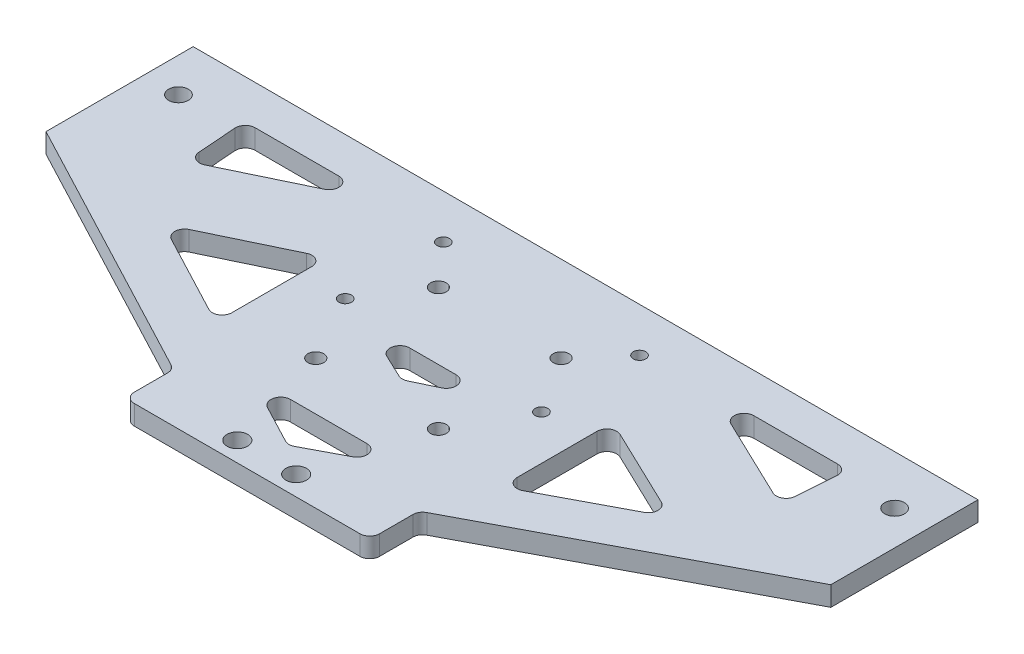
SolidWorks part; units mm, degrees
material "Thornel Mat VMA"
ref_plane "Front" through (0, 0, 0) normal (0, 0, 1) x (1, 0, 0)
ref_plane "Top" through (0, 0, 0) normal (0, 1, 0) x (1, 0, 0)
ref_plane "Right" through (0, 0, 0) normal (1, 0, 0) x (0, 0, -1)
sketch "草图1" plane through (0, 0, 0) normal (0, 1, 0) x (1, 0, 0)
  line L0 (0, 40.0348) -> (0, 0) construction
  line L1 (25, 0) -> (-25, 0)
  line L2 (-25, 0) -> (-80, 29)
  line L3 (-80, 29) -> (-80, 59)
  line L4 (-80, 59) -> (80, 59)
  line L5 (80, 29) -> (80, 59)
  line L6 (25, 0) -> (80, 29)
  point P9 (0, 59)
  dimension "D1" = 59
  dimension "D2" = 80
  dimension "D3" = 25
  dimension "D4" = 30
extrude "凸台-拉伸1" add sketch "草图1" along normal blind 4
sketch "草图2" plane through (0, 4, 0) normal (0, 1, 0) x (1, 0, 0)
  line L0 (0, 0) -> (0, 59) construction
  line L1 (80, 59) -> (-80, 59) construction
  line L2 (-12.5, 41.5) -> (-12.5, 16.5) construction
  line L3 (-12.5, 29) -> (12.5, 29) construction
  line L4 (12.5, 41.5) -> (12.5, 16.5) construction
  circle A0 centre (-12.5, 41.5) radius 1.6
  circle A3 centre (12.5, 41.5) radius 1.6
  circle A4 centre (-12.5, 16.5) radius 1.6
  circle A5 centre (12.5, 16.5) radius 1.6
  point P14 (0, 29)
  dimension "D1" = 3.2
  dimension "D2" = 25
  dimension "D4" = 17.5
  dimension "D3" = 12.5
extrude "切除-拉伸1" cut sketch "草图2" against normal through all
sketch "草图3" plane through (0, 4, 0) normal (0, 1, 0) x (1, 0, 0)
  line L0 (-80, 59) -> (-80, 29) construction
  line L1 (80, 59) -> (-80, 59) construction
  line L23 (-25, 0) -> (25, 0) construction
  line L24 (-66, 51.4654) -> (-66, 27.9182)
  line L25 (-65.4092, 27.0057) -> (-27.5283, 10.0199)
  line L26 (-26.3885, 11.6151) -> (-64.2694, 52.1482)
  line L27 (-56.7306, 52.8689) -> (-35.4528, 30.1014)
  line L28 (-33.7222, 30.7842) -> (-33.7222, 50.1473)
  line L29 (-34.5642, 51.1347) -> (-55.842, 54.5392)
  line L32 (-22.9874, 9.4403) -> (-26.732, 36.0544)
  line L33 (-80, 29) -> (-25, 0) construction
  line L34 (-13.5, 37) -> (-13.5, 17) construction
  line L35 (-28.7222, 35.9151) -> (-28.7222, 11.1733)
  line L36 (-28.1694, 10.2789) -> (-24.4249, 8.4066)
  line L37 (-13.5, 37) -> (-12.5, 41.5) construction
  line L38 (-4.3247, 7.5552) -> (-22.7222, 7.5552) construction
  line L39 (0, 30) -> (0, 0) construction
  line L40 (4.3247, 7.5552) -> (22.7222, 7.5552) construction
  line L41 (7.5, 20.5) -> (7.5, 10.5) construction
  line L42 (28.1694, 10.2789) -> (24.4249, 8.4066)
  line L43 (28.7222, 35.9151) -> (28.7222, 11.1733)
  line L44 (22.9874, 9.4403) -> (26.732, 36.0544)
  line L45 (34.5642, 51.1347) -> (55.842, 54.5392)
  line L46 (33.7222, 30.7842) -> (33.7222, 50.1473)
  line L47 (56.7306, 52.8689) -> (35.4528, 30.1014)
  line L48 (26.3885, 11.6151) -> (64.2694, 52.1482)
  line L49 (65.4092, 27.0057) -> (27.5283, 10.0199)
  line L50 (66, 51.4654) -> (66, 27.9182)
  line L51 (-12.5, 16.5) -> (-13.5, 17) construction
  circle A0 centre (-73, 51) radius 2.6
  arc A1 (-24.4249, 8.4066) -> (-22.9874, 9.4403) centre (-23.9777, 9.301) ccw
  arc A2 (-28.7222, 11.1733) -> (-28.1694, 10.2789) centre (-27.7222, 11.1733) ccw
  arc A3 (-28.7222, 35.9151) -> (-26.732, 36.0544) centre (-27.7222, 35.9151) cw
  arc A4 (-33.7222, 50.1473) -> (-34.5642, 51.1347) centre (-34.7222, 50.1473) ccw
  arc A5 (-56.7306, 52.8689) -> (-55.842, 54.5392) centre (-56, 53.5517) cw
  arc A6 (-35.4528, 30.1014) -> (-33.7222, 30.7842) centre (-34.7222, 30.7842) ccw
  arc A7 (-26.3885, 11.6151) -> (-27.5283, 10.0199) centre (-27.1191, 10.9323) cw
  arc A8 (-66, 27.9182) -> (-65.4092, 27.0057) centre (-65, 27.9182) ccw
  arc A9 (-66, 51.4654) -> (-64.2694, 52.1482) centre (-65, 51.4654) cw
  arc A10 (66, 51.4654) -> (64.2694, 52.1482) centre (65, 51.4654) ccw
  arc A11 (66, 27.9182) -> (65.4092, 27.0057) centre (65, 27.9182) cw
  arc A12 (26.3885, 11.6151) -> (27.5283, 10.0199) centre (27.1191, 10.9323) ccw
  arc A13 (35.4528, 30.1014) -> (33.7222, 30.7842) centre (34.7222, 30.7842) cw
  arc A14 (56.7306, 52.8689) -> (55.842, 54.5392) centre (56, 53.5517) ccw
  arc A15 (33.7222, 50.1473) -> (34.5642, 51.1347) centre (34.7222, 50.1473) cw
  arc A16 (28.7222, 35.9151) -> (26.732, 36.0544) centre (27.7222, 35.9151) ccw
  arc A17 (28.7222, 11.1733) -> (28.1694, 10.2789) centre (27.7222, 11.1733) cw
  arc A18 (24.4249, 8.4066) -> (22.9874, 9.4403) centre (23.9777, 9.301) cw
  circle A19 centre (73, 51) radius 2.6
  circle A20 centre (-13.5, 17) radius 1.6
  circle A21 centre (-13.5, 37) radius 1.6
  circle A22 centre (13.5, 17) radius 1.6
  circle A23 centre (13.5, 37) radius 1.6
  point P24 (-28.7222, 10.5552)
  point P32 (-28.7222, 50.2)
  point P35 (-33.7222, 51)
  point P38 (-58.7222, 55)
  point P43 (-23, 7.9894)
  point P46 (-66, 27.2707)
  point P49 (-66, 54)
  point P86 (66, 54)
  point P87 (66, 27.2707)
  point P88 (23, 7.9894)
  point P89 (58.7222, 55)
  point P90 (33.7222, 51)
  point P91 (28.7222, 50.2)
  point P92 (28.7222, 10.5552)
  dimension "D1" = 5.2
  dimension "D2" = 7
  dimension "D3" = 8
  dimension "D15" = 1
  dimension "D16" = 3.2
  dimension "D17" = 27
  dimension "D18" = 17
  dimension "D20" = 3.2
  dimension "D4" = 7
  dimension "D5" = 5
  dimension "D6" = 5
  dimension "D7" = 8
  dimension "D8" = 6
  dimension "D9" = 4
  dimension "D10" = 8
  dimension "D11" = 2
  dimension "D12" = 5
  dimension "D13" = 25
  dimension "D14" = 6
  dimension "D19" = 20
extrude "切除-拉伸2" [suppressed] cut sketch "草图3" against normal through all
fillet "圆角1" [suppressed] radius 7
sketch "草图4" plane through (0, 4, 0) normal (0, 1, 0) x (1, 0, 0)
  line L0 (0, 0) -> (0, 67.0073) construction
  line L1 (80, 59) -> (-80, 59) construction
  circle A0 centre (20, 50) radius 1.275
  circle A2 centre (20, 30) radius 1.275
  circle A3 centre (-20, 30) radius 1.275
  circle A4 centre (-20, 50) radius 1.275
  dimension "D1" = 2.55
  dimension "D2" = 20
  dimension "D4" = 9
  dimension "D5" = 20
  dimension "D3" = 2
extrude "切除-拉伸3" cut sketch "草图4" against normal blind 10
sketch "草图6" plane through (0, 4, 0) normal (0, 1, 0) x (1, 0, 0)
  line L1 (-25, 0) -> (25, 0)
  line L2 (-25, 0) -> (-25, -10)
  line L3 (-25, -10) -> (25, -10)
  line L4 (25, 0) -> (25, -10)
  dimension "D1" = 50
  dimension "D2" = 10
extrude "凸台-拉伸2" add sketch "草图6" against normal up to surface (4 mm away) up to face at (-20, 0, -51.275)
sketch "草图7" plane through (0, 4, 0) normal (0, 1, 0) x (1, 0, 0)
  line L0 (0, 0) -> (0, -33.3189) construction
  line L1 (-25, -10) -> (25, -10) construction
  circle A0 centre (-6, -6) radius 2.1
  circle A1 centre (6, -6) radius 2.1
  dimension "D1" = 4.2
  dimension "D2" = 6
  dimension "D3" = 4
extrude "切除-拉伸4" cut sketch "草图7" against normal blind 10
sketch "草图8" plane through (0, 4, 0) normal (0, 1, 0) x (1, 0, 0)
  line L0 (-80, 59) -> (-80, 29) construction
  line L1 (80, 59) -> (-80, 59) construction
  line L2 (0, 0) -> (0, 67.9824) construction
  circle A0 centre (-73, 49) radius 2
  circle A1 centre (73, 49) radius 2
  dimension "D1" = 4
  dimension "D2" = 7
  dimension "D3" = 10
extrude "切除-拉伸5" cut sketch "草图8" against normal blind 10
sketch "草图9" plane through (0, 4, 0) normal (0, 1, 0) x (1, 0, 0)
  line L0 (0, 0) -> (0, 79.7791) construction
  line L1 (-13.6072, 27.8756) -> (13.6072, 27.8756)
  line L2 (-13.6072, 27.8756) -> (0, 21.4248)
  line L3 (-61.5112, 51) -> (-33.5112, 51)
  line L4 (-33.5112, 51) -> (-60.5648, 38.0345)
  line L5 (-60.5648, 38.0345) -> (-61.5112, 51)
  line L6 (-51.7088, 24.599) -> (-29.0798, 35.444)
  line L7 (-29.0798, 35.444) -> (-29.0798, 12.6673)
  line L8 (-29.0798, 12.6673) -> (-51.7088, 24.599)
  line L9 (29.0798, 12.6673) -> (51.7088, 24.599)
  line L10 (29.0798, 35.444) -> (29.0798, 12.6673)
  line L11 (51.7088, 24.599) -> (29.0798, 35.444)
  line L12 (60.5648, 38.0345) -> (61.5112, 51)
  line L13 (33.5112, 51) -> (60.5648, 38.0345)
  line L14 (61.5112, 51) -> (33.5112, 51)
  line L15 (13.6072, 27.8756) -> (0, 21.4248)
  line L16 (80, 59) -> (-80, 59) construction
  line L17 (-80, 29) -> (-25, 0) construction
  line L18 (-80, 59) -> (-80, 29) construction
  point P19 (0, 27.8756)
  point P21 (0, 21.4248)
  point P22 (-13.8231, 27.978)
  point P23 (-25.0864, 10.3663)
  point P24 (-51.7088, 24.599)
  point P29 (-32.766, 51)
  point P30 (-60.0027, 38.0345)
  dimension "D1" = 28
  dimension "D2" = 8
  dimension "D3" = 13
  dimension "D4" = 30
extrude "切除-拉伸6" cut sketch "草图9" against normal blind 10
sketch "草图10" plane through (0, 4, 0) normal (0, 1, 0) x (1, 0, 0)
  line L0 (0, 0) -> (0, -26.7425) construction
  line L1 (0, 0) -> (0, 25.9451) construction
  line L2 (-15.8628, 6.6366) -> (15.8628, 6.6366)
  line L3 (15.8628, 6.6366) -> (0, -1.7274)
  line L4 (25, 0) -> (80, 29) construction
  line L5 (-15.8628, 6.6366) -> (0, -1.7274)
  point P11 (0, 6.6366)
extrude "切除-拉伸7" cut sketch "草图10" against normal blind 10
fillet "圆角2" radius 2 22 edges at (-25, 2, 0) (-25, 2, 10) (25, 2, 10) (25, 2, 0) (-13.6072, 2, -27.8756) (13.6072, 2, -27.8756) (0, 2, -21.4248) (-51.7088, 2, -24.599) (-29.0798, 2, -35.444) (-29.0798, 2, -12.6673) (-61.5112, 2, -51) (-33.5112, 2, -51) (-60.5648, 2, -38.0345) (33.5112, 2, -51) (61.5112, 2, -51) (60.5648, 2, -38.0345) (29.0798, 2, -35.444) (51.7088, 2, -24.599) (0, 2, 1.7274) (-15.8628, 2, -6.6366) (15.8628, 2, -6.6366) (29.0798, 2, -12.6673)
